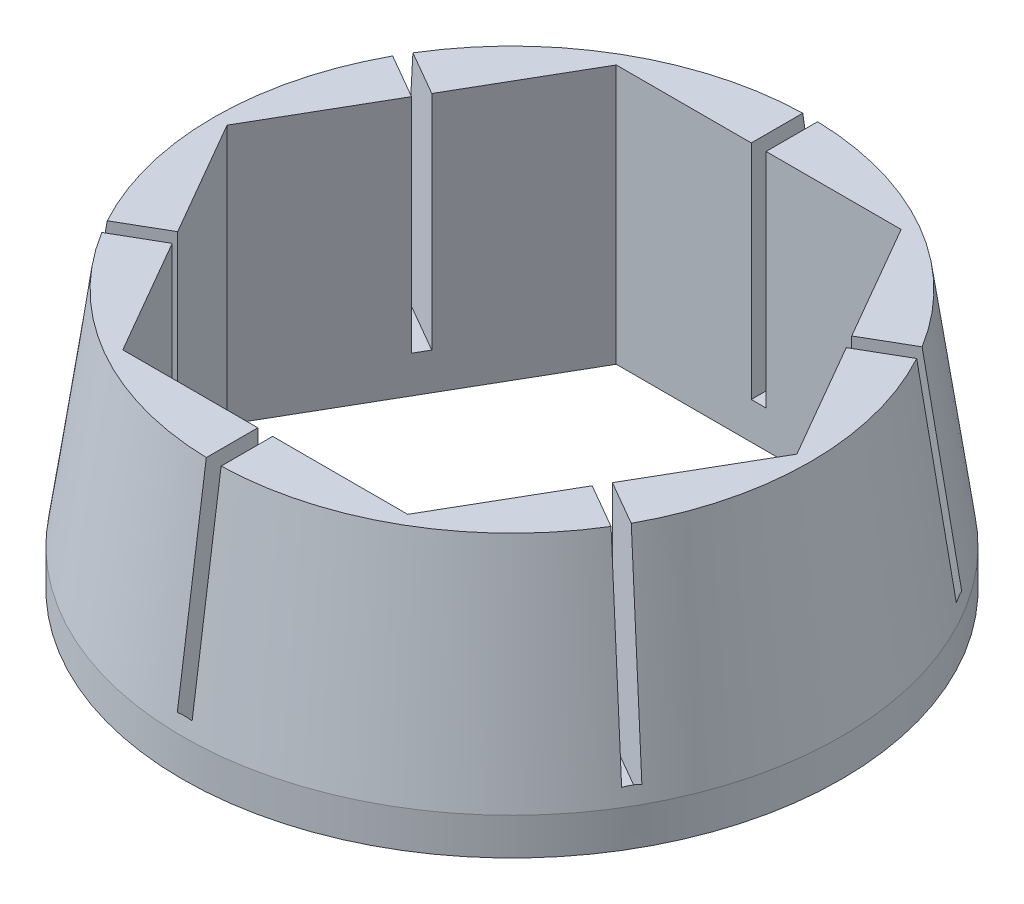
SolidWorks part; units mm, degrees
ref_plane "Front Plane" through (0, 0, 0) normal (0, 0, 1) x (1, 0, 0)
ref_plane "Top Plane" through (0, 0, 0) normal (0, 1, 0) x (1, 0, 0)
ref_plane "Right Plane" through (0, 0, 0) normal (1, 0, 0) x (0, 0, -1)
sketch "J1_Collet_Outer_Profile" plane through (0, 0, 0) normal (0, 0, 1) x (1, 0, 0)
  line L0 (0, 12) -> (0, -2) construction
  line L7 (0, 12) -> (16.1135, 12)
  line L8 (16.1135, 12) -> (17.8, 0)
  line L9 (17.8, 0) -> (0, 0)
  line L10 (0, -2) -> (17.8, -2)
  line L11 (17.8, 0) -> (17.8, -2)
  dimension "D1" = 16.1135
  dimension "D2" = 12
  dimension "D4" = 17.8
  dimension "D3" = 2
revolve "J1_Collet_Blank" add sketch "J1_Collet_Outer_Profile" angle 360 about L0 region at (8.4854, 5.9005, 0) region at (8.9, -1, 0)
sketch "J1_Collet_Hex_Bore_Profile" plane through (0, -2, 0) normal (0, -1, 0) x (1, 0, 0)
  line L1 (15.3864, 0) -> (7.6932, 13.325)
  line L2 (7.6932, 13.325) -> (-7.6932, 13.325)
  line L3 (-7.6932, 13.325) -> (-15.3864, 0)
  line L4 (-15.3864, 0) -> (-7.6932, -13.325)
  line L5 (-7.6932, -13.325) -> (7.6932, -13.325)
  line L6 (7.6932, -13.325) -> (15.3864, 0)
  circle A0 centre (0, 0) radius 13.325 construction
  dimension "D1" = 26.65
extrude "J1_Collet_Hex_Bore" cut sketch "J1_Collet_Hex_Bore_Profile" against normal through all
sketch "J1_Collet_Master_Slit_Profile" plane through (0, 12, 0) normal (0, 1, 0) x (1, 0, 0)
  line L0 (14.8044, 8.5473) -> (0, 0) construction
  line L25 (11.5666, 6.2161) -> (15.1062, 9.1834) construction
  line L32 (11.1666, 6.9089) -> (15.1062, 9.1834)
  line L34 (15.5062, 8.4906) -> (11.1666, 6.9089) construction
  line L37 (11.1666, 6.9089) -> (11.5666, 6.2161)
  line L38 (11.5666, 6.2161) -> (15.5062, 8.4906)
  line L39 (15.5062, 8.4906) -> (15.1062, 9.1834)
  line L40 (7.6932, 13.325) -> (15.3864, 0) construction
  point P2 (13.3364, 7.6998)
  point P11 (15.4059, 8.8643)
  point P22 (13.8035, 8.2559)
  dimension "D1" = 0.8
  dimension "D4" = 30
  dimension "D2" = 0.1
extrude "J1_Collet_Master_Slit" cut sketch "J1_Collet_Master_Slit_Profile" against normal blind 12
ref_axis "J1_Collet_Center_Axis" through (0, -21.8283, 0) along (0, 1, 0)
pattern_circular "J1_Collet_Slit_Pattern" count 6 over 360 about axis through (0, -21.8283, 0) along (0, 1, 0) of "J1_Collet_Master_Slit"
equation "\"AF\"=32"
equation "\"wall\"=2.00mm"
equation "\"clr\"=0.45mm"
equation "\"step\"=4.45mm"
equation "\"tail_h\"=6"
equation "\"stop_h\"=6"
equation "\"relief\"=0.60mm"
equation "\"stop_top\"=33.00mm"
equation "\"boss_h\"= 8mm"
equation "\"finger_L\"= 12mm"
equation "\"collet_h\"= 14mm"
equation "\"collar_h\"= 22mm"
equation "\"thread_pitch\"= 3mm"
equation "\"thread_depth\"= 1.4mm"
equation "\"cone_half_angle\"= 8deg"
equation "\"lip_clr\"= .3mm"
equation "\"J1_Thread_Major_Dia\"= 38.1mm"
equation "\"J1_Thread_Root_Dia\"= 35.3mm"
equation "\"collet_slit_w\"= .8mm"
equation "\"collet_bore_AF1\"= 26.65mm"
equation "\"lip_ring_h\"= 2mm"
equation "\"collet_base_OD1\"= 35.6mm"
equation "\"collet_top_OD1\"= \"collet_base_OD1\" - 2 * \"finger_L\" * tan ( \"cone_half_angle\" ) - 1mm + 1mm"
equation "\"J1_Nut_Cone_Base_ID\"= 35.8mm"
equation "\"J1_Nut_Cone_Top_ID\"= \"J1_Nut_Cone_Base_ID\" - 2 * \"finger_L\" * tan ( \"cone_half_angle\" ) + 1mm - 1mm"
equation "\"D1@J1_Collet_Outer_Profile\" = \"collet_top_OD1\" / 2"
equation "\"D2@J1_Collet_Outer_Profile\" = \"finger_L\""
equation "\"D4@J1_Collet_Outer_Profile\" = \"collet_base_OD1\" / 2"
equation "\"D3@J1_Collet_Outer_Profile\" = \"lip_ring_h\""
equation "\"D1@J1_Collet_Hex_Bore_Profile\" = \"collet_bore_AF1\""
equation "\"D1@J1_Collet_Master_Slit_Profile\" = \"collet_slit_w\""
equation "\"D1@J1_Collet_Master_Slit\"=\"finger_L\""
equation "\"D19@T2_Upper_Body_Relief\" = 165 + \"stop_top\""
equation "\"D19@T3_Lower_Body_Relief\" = \"tail_h\""
